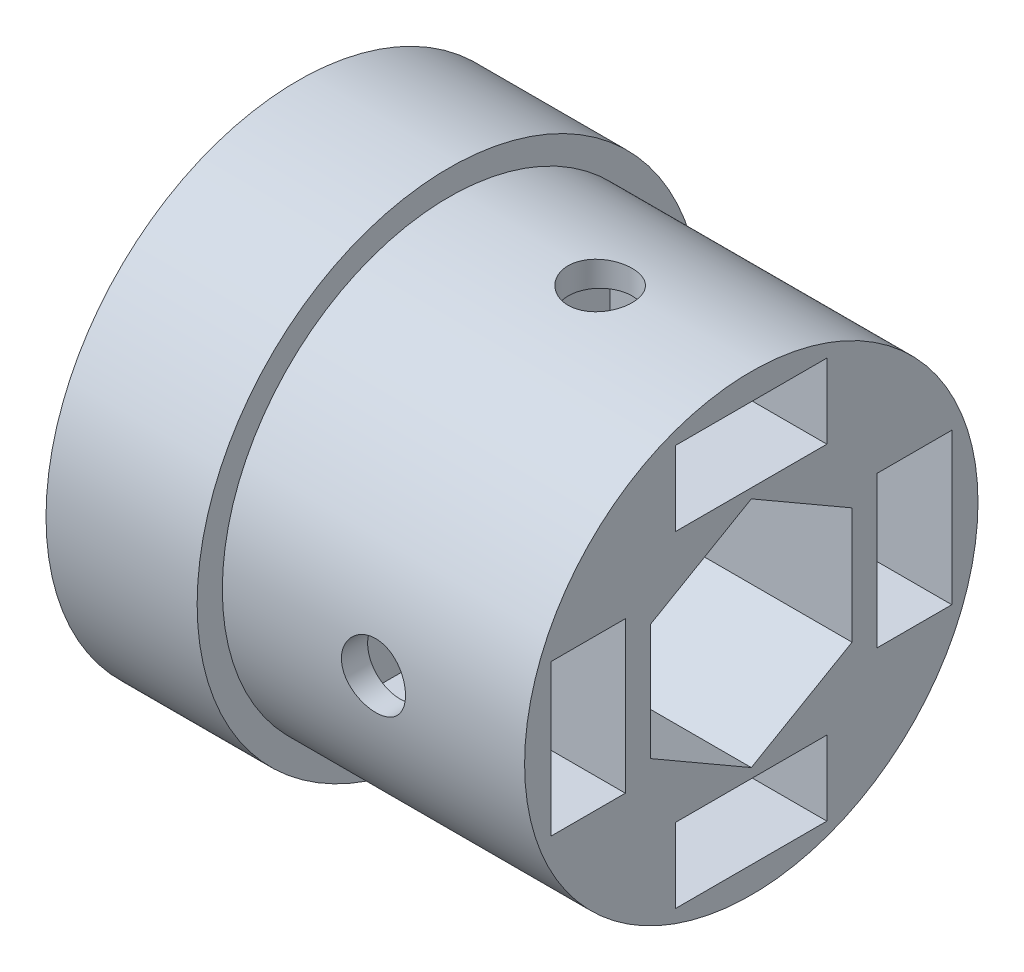
SolidWorks part; units mm, degrees
material "6061-T6 (SS)"
ref_plane "Front Plane" through (0, 0, 0) normal (0, 0, 1) x (1, 0, 0)
ref_plane "Top Plane" through (0, 0, 0) normal (0, 1, 0) x (1, 0, 0)
ref_plane "Right Plane" through (0, 0, 0) normal (1, 0, 0) x (0, 0, -1)
sketch "Sketch1" plane through (0, 0, 0) normal (1, 0, 0) x (0, 0, -1)
  circle A0 centre (0, 0) radius 14.2875
  dimension "D1" = 28.575
extrude "Boss-Extrude1" add sketch "Sketch1" along normal blind 19.05
sketch "Sketch2" plane through (0, 0, 0) normal (-1, 0, 0) x (0, 0, 1)
  circle A0 centre (0, 0) radius 15.875
  dimension "D1" = 31.75
extrude "Boss-Extrude2" add sketch "Sketch2" along normal blind 9.525
sketch "Sketch3" plane through (-9.525, 0, 0) normal (-1, 0, 0) x (0, 0, 1)
  circle A0 centre (0, 0) radius 11.1125
  dimension "D1" = 22.225
sketch "Sketch4" plane through (-9.525, 0, 0) normal (-1, 0, 0) x (0, 0, 1)
  line L1 (0, 7.3323) -> (-6.35, 3.6662)
  line L2 (-6.35, 3.6662) -> (-6.35, -3.6662)
  line L3 (-6.35, -3.6662) -> (0, -7.3323)
  line L4 (0, -7.3323) -> (6.35, -3.6662)
  line L5 (6.35, -3.6662) -> (6.35, 3.6662)
  line L6 (6.35, 3.6662) -> (0, 7.3323)
  circle A0 centre (0, 0) radius 6.35 construction
  dimension "D1" = 12.7
extrude "Cut-Extrude1" cut sketch "Sketch4" against normal through all
sketch "Sketch5" plane through (0, 0, 0) normal (0, 0, 1) x (1, 0, 0)
  circle A0 centre (9.525, 0) radius 2.0193
  dimension "D1" = 4.0386
  dimension "D2" = 9.525
extrude "Cut-Extrude2" cut sketch "Sketch5" against normal through all both and the other way through all
sketch "Sketch6" plane through (0, 0, 0) normal (0, 1, 0) x (1, 0, 0)
  circle A0 centre (9.525, 0) radius 2.0193
  dimension "D1" = 4.0386
  dimension "D2" = 9.525
extrude "Cut-Extrude3" cut sketch "Sketch6" against normal through all both and the other way through all
sketch "Sketch7" plane through (19.05, 0, 0) normal (1, 0, 0) x (0, 0, -1)
  line L0 (4.7625, -7.9375) -> (-4.7625, -7.9375)
  line L1 (7.9375, 4.7625) -> (12.6365, 4.7625)
  line L2 (7.9375, 4.7625) -> (7.9375, -4.7625)
  line L3 (7.9375, -4.7625) -> (12.6365, -4.7625)
  line L4 (12.6365, 4.7625) -> (12.6365, -4.7625)
  line L5 (4.7625, -7.9375) -> (4.7625, -12.6365)
  line L6 (4.7625, -12.6365) -> (-4.7625, -12.6365)
  line L7 (-4.7625, -7.9375) -> (-4.7625, -12.6365)
  line L8 (-7.9375, -4.7625) -> (-7.9375, 4.7625)
  line L9 (-7.9375, -4.7625) -> (-12.6365, -4.7625)
  line L10 (-12.6365, -4.7625) -> (-12.6365, 4.7625)
  line L11 (-7.9375, 4.7625) -> (-12.6365, 4.7625)
  line L12 (-4.7625, 7.9375) -> (4.7625, 7.9375)
  line L13 (-4.7625, 7.9375) -> (-4.7625, 12.6365)
  line L14 (-4.7625, 12.6365) -> (4.7625, 12.6365)
  line L15 (4.7625, 7.9375) -> (4.7625, 12.6365)
  point P4 (12.6365, 0)
  point P21 (0, 0)
  dimension "D1" = 4.699
  dimension "D2" = 9.525
  dimension "D3" = 7.9375
  dimension "D4" = 4
extrude "Cut-Extrude4" cut sketch "Sketch7" against normal blind 13.6525 and the other way through all
